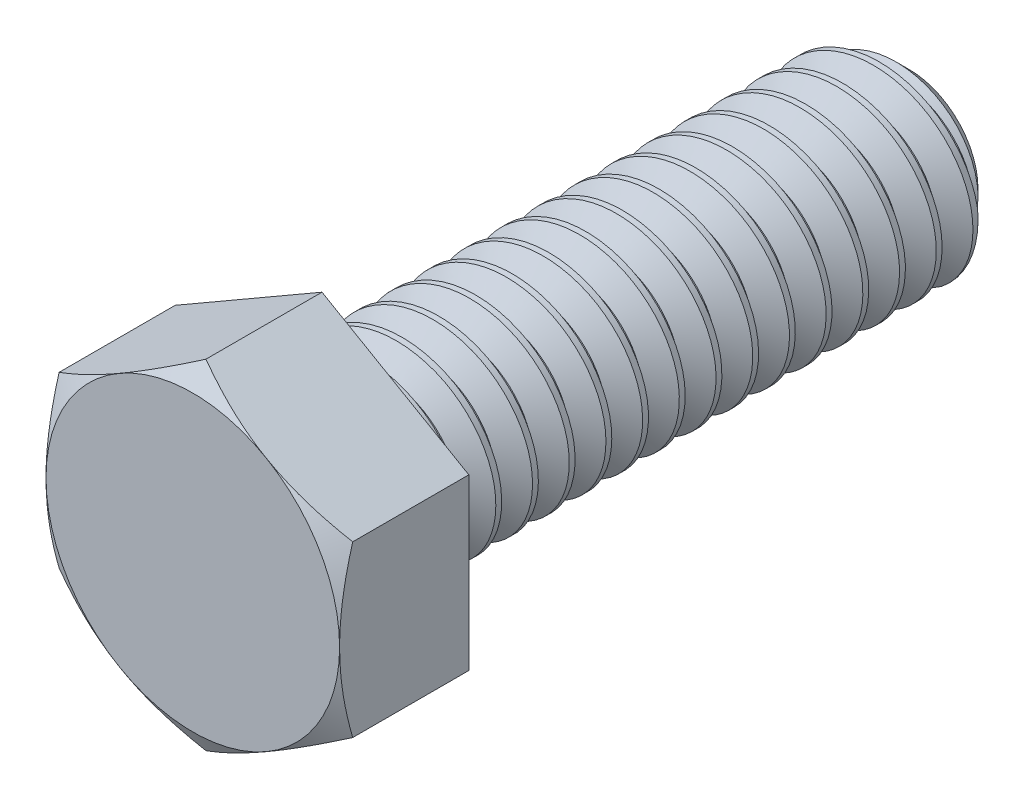
SolidWorks part; units mm, degrees
material "AISI 304"
ref_plane "Front" through (0, 0, 0) normal (0, 0, 1) x (1, 0, 0)
ref_plane "Top" through (0, 0, 0) normal (0, 1, 0) x (1, 0, 0)
ref_plane "Right" through (0, 0, 0) normal (1, 0, 0) x (0, 0, -1)
sketch "Sketch1" plane through (0, 0, 0) normal (0, 0, 1) x (1, 0, 0)
  line L1 (-3.175, -1.8331) -> (0, -3.6662)
  line L2 (0, -3.6662) -> (3.175, -1.8331)
  line L3 (3.175, -1.8331) -> (3.175, 1.8331)
  line L4 (3.175, 1.8331) -> (0, 3.6662)
  line L5 (0, 3.6662) -> (-3.175, 1.8331)
  line L6 (-3.175, 1.8331) -> (-3.175, -1.8331)
  circle A0 centre (0, 0) radius 3.175 construction
  circle A1 centre (0, 0) radius 3.175 construction
  dimension "Head Dia" = 6.35
extrude "Extrude3" add sketch "Sketch1" along normal blind 2.794
sketch "Sketch4" plane through (0, 0, 0) normal (1, 0, 0) x (0, 0, -1)
  line L0 (0, 0) -> (12.7, 0)
  line L3 (12.7, 0) -> (12.7, 2.0828)
  line L4 (12.7, 2.0828) -> (0, 2.0828)
  line L6 (0, 2.0828) -> (0, 0)
  line L9 (12.7, 2.0828) -> (12.7, -2.0828) construction
  dimension "length" = 12.7
  dimension "dia" = 4.1656
revolve "Revolve1" add sketch "Sketch4" angle 360 about L0
sketch "Sketch13" plane through (0, 0, -12.7) normal (0, 0, -1) x (-1, 0, 0)
  circle A2 centre (0, 0) radius 2.0828
curve "Helix/Spiral1" pitch 0.7937 height 15.494 radius 2.0828 centre (0, 0, -12.7) axis (0, 0, 1) start towards (1, 0, 0)
chamfer "Chamfer2" distance 0.5953 angle 45 1 edges at (2.0828, 0, -12.7)
sketch "Sketch14" plane through (0, 0, 0) normal (1, 0, 0) x (0, 0, -1)
  line L0 (12.7, 2.1076) -> (13.3945, 2.1076)
  line L1 (13.3945, 2.1076) -> (13.0969, 1.5706)
  line L2 (13.0969, 1.5706) -> (12.9977, 1.5706)
  line L3 (12.9977, 1.5706) -> (12.7, 2.1076)
  line L4 (12.8488, 1.8391) -> (13.2457, 1.8391) construction
  dimension "D1" = 0.0992
  dimension "D2" = 58
  dimension "D3" = 0.3969
  dimension "D4" = 0.0248
sweep "Cut-Sweep1" cut profiles "Sketch14" path "Helix/Spiral1" align with end faces yes
ref_plane "Plane1" through (0, 0, 25.4) normal (0, 0, -1) x (-1, 0, 0)
sketch "Sketch29" [suppressed] plane through (0, 0, 28.575) normal (0, 0, -1) x (-1, 0, 0)
  circle A0 centre (0, 0) radius 1.7526 construction
  circle A1 centre (0, 0) radius 1.7526
  point P3 (0, -1.7526)
  point P4 (0, 1.7526)
extrude "Extrude11" [suppressed] add sketch "Sketch29" against normal up to surface (28.575 mm away) up to plane "Front"
sketch "Sketch26" plane through (0, 0, 0) normal (0, 0, 1) x (1, 0, 0)
  circle A1 centre (0, 0) radius 0.5461
  dimension "D1" = 1.0922
extrude "Extrude12" add sketch "Sketch26" along normal up to surface (2.794 mm away) up to face at (0, 0, 2.794)
sketch "Sketch30" plane through (0, 0, 2.794) normal (0, 0, 1) x (1, 0, 0)
  circle A0 centre (0, 0) radius 3.175 construction
  circle A1 centre (0, 0) radius 3.175
extrude "Extrude13" cut sketch "Sketch30" against normal blind 2.54 draft 60 flip side to cut
sketch "Sketch18" plane through (0, 0, 0) normal (1, 0, 0) x (0, 0, -1)
  line L1 (12.7, 2.0828) -> (0, 2.0828) construction
  line L2 (-2.794, 3.175) -> (-2.794, 2.7496) construction
  point P0 (11.5094, -2.0828)
  point P1 (11.9062, 2.0828)
  point P2 (-2.794, 3.6662)
  dimension "D1" = 0.7937
  dimension "D2" = 1.1906
equation "\"D3@Helix/Spiral1\" = \"length@Sketch4\" + \"Head Ht@Extrude3\""
equation "\"D1@Sketch14\" = \"D4@Helix/Spiral1\" * .125"
equation "\"D3@Sketch14\" = \"D4@Helix/Spiral1\" * .5"
equation "\"D4@Sketch14\" = \"D1@Sketch14\" * .25"
equation "\"D1@Chamfer2\" = \"D4@Helix/Spiral1\" * .75"
equation "\"D1@Sketch18\" = \"D4@Helix/Spiral1\""
equation "\"D2@Sketch18\" = \"D4@Helix/Spiral1\" * 1.5"
